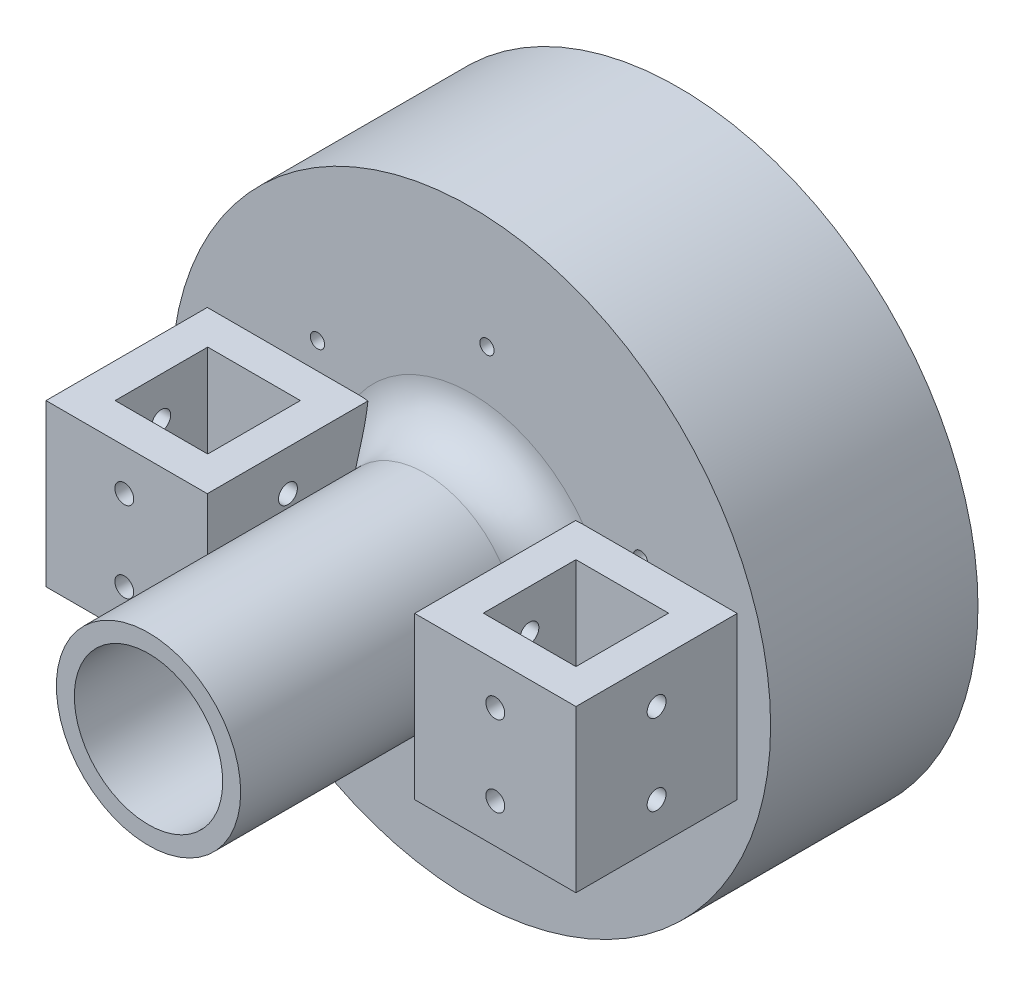
SolidWorks part; units mm, degrees
ref_plane "Front Plane" through (0, 0, 0) normal (0, 0, 1) x (1, 0, 0)
ref_plane "Top Plane" through (0, 0, 0) normal (0, 1, 0) x (1, 0, 0)
ref_plane "Right Plane" through (0, 0, 0) normal (1, 0, 0) x (0, 0, -1)
sketch "Sketch1" plane through (0, 0, 0) normal (0, 0, 1) x (1, 0, 0)
  line L0 (-60.923, -22.6581) -> (60.923, 22.6581) construction
  circle A0 centre (0, 0) radius 65
  circle A6 centre (-3.4488, -40.4788) radius 1.55
  circle A7 centre (0, 0) radius 16.5
  circle A11 centre (-36.7801, -17.2527) radius 1.55
  circle A12 centre (-33.3313, 23.2262) radius 1.55
  circle A13 centre (3.4488, 40.4788) radius 1.55
  circle A14 centre (36.7801, 17.2527) radius 1.55
  circle A15 centre (33.3313, -23.2262) radius 1.55
  point P18 (0, 0)
  point P20 (0, 0)
  point P36 (0, 0)
  dimension "D1" = 130
  dimension "D2" = 6
  dimension "D5" = 33
  dimension "D3" = 40.6255
extrude "Boss-Extrude1" add sketch "Sketch1" along normal blind 10
sketch "Sketch2" plane through (0, 0, 10) normal (0, 0, 1) x (1, 0, 0)
  circle A0 centre (0, 0) radius 20
  circle A1 centre (0, 0) radius 16.1
  dimension "D1" = 40
  dimension "D2" = 32.2
extrude "Boss-Extrude2" add sketch "Sketch2" along normal blind 70
sketch "Sketch3" plane through (0, 0, 0) normal (0, 0, -1) x (-1, 0, 0)
  circle A0 centre (0, 0) radius 45.25
  circle A1 centre (0, 0) radius 65
  dimension "D1" = 90.5
extrude "Boss-Extrude3" add sketch "Sketch3" along normal blind 35
sketch "Sketch4" plane through (0, 0, 10) normal (0, 0, 1) x (1, 0, 0)
  line L0 (-65, 0) -> (65, 0) construction
  line L1 (-57.2457, 17.5) -> (-22.2457, 17.5)
  line L2 (-57.2457, 17.5) -> (-57.2457, -17.5)
  line L3 (-57.2457, -17.5) -> (-22.2457, -17.5)
  line L4 (-22.2457, 17.5) -> (-22.2457, -17.5)
  line L5 (-57.2457, 17.5) -> (-22.2457, -17.5) construction
  line L6 (-57.2457, -17.5) -> (-22.2457, 17.5) construction
  line L7 (22.7543, 17.5) -> (57.7543, 17.5)
  line L8 (22.7543, 17.5) -> (22.7543, -17.5)
  line L9 (22.7543, -17.5) -> (57.7543, -17.5)
  line L10 (57.7543, 17.5) -> (57.7543, -17.5)
  line L11 (22.7543, 17.5) -> (57.7543, -17.5) construction
  line L12 (22.7543, -17.5) -> (57.7543, 17.5) construction
  circle A0 centre (40.3888, -6.3107) radius 1.55 construction
  circle A1 centre (-39.7457, -0.7631) radius 1.55 construction
  circle A2 centre (0, 0) radius 65 construction
  point P21 (40.2543, 0)
  point P22 (-39.7457, 0)
  point P23 (-22.2457, 0)
  dimension "D1" = 35
  dimension "D2" = 35
  dimension "D3" = 35
  dimension "D4" = 35
  dimension "D5" = 45
  dimension "D6" = 22.2457
extrude "Boss-Extrude4" add sketch "Sketch4" along normal blind 35
sketch "Sketch5" plane through (0, 17.5, 0) normal (0, 1, 0) x (1, 0, 0)
  line L0 (57.7543, -45) -> (57.7543, -10) construction
  line L1 (30.1543, -17.4) -> (50.2543, -17.4)
  line L2 (30.1543, -17.4) -> (30.1543, -37.5)
  line L3 (30.1543, -37.5) -> (50.2543, -37.5)
  line L4 (50.2543, -17.4) -> (50.2543, -37.5)
  line L5 (30.1543, -17.4) -> (50.2543, -37.5) construction
  line L6 (30.1543, -37.5) -> (50.2543, -17.4) construction
  line L7 (-49.7457, -17.4) -> (-29.6457, -17.4)
  line L8 (-49.7457, -17.4) -> (-49.7457, -37.5)
  line L9 (-49.7457, -37.5) -> (-29.6457, -37.5)
  line L10 (-29.6457, -17.4) -> (-29.6457, -37.5)
  line L11 (-49.7457, -17.4) -> (-29.6457, -37.5) construction
  line L12 (-49.7457, -37.5) -> (-29.6457, -17.4) construction
  line L13 (57.7543, -45) -> (22.7543, -45) construction
  line L14 (-57.2457, -45) -> (-57.2457, -10) construction
  line L15 (-22.2457, -45) -> (-57.2457, -45) construction
  point P0 (40.2043, -27.45)
  point P5 (-39.6957, -27.45)
  dimension "D1" = 20.1
  dimension "D2" = 20.1
  dimension "D3" = 7.5
  dimension "D4" = 7.5
  dimension "D5" = 20.1
  dimension "D6" = 20.1
  dimension "D7" = 7.5
  dimension "D8" = 7.5
extrude "Cut-Extrude1" cut sketch "Sketch5" against normal blind 40
fillet "Fillet1" radius 10 1 edges at (20, 0, 10)
sketch "Sketch6" plane through (57.7543, 0, 0) normal (1, 0, 0) x (0, 0, -1)
  line L0 (-27.5, 17.5) -> (-27.5, -17.5) construction
  line L1 (-45, 17.5) -> (-10, 17.5) construction
  line L2 (-45, -17.5) -> (-10, -17.5) construction
  line L3 (-45, 0) -> (-10, 0) construction
  line L4 (-45, -17.5) -> (-45, 17.5) construction
  line L5 (-10, 65) -> (-10, -65) construction
  circle A0 centre (-27.5, 8.75) radius 2.05
  circle A1 centre (-27.5, -8.75) radius 2.05
  point P16 (-27.5, 0)
  dimension "D1" = 4.1
  dimension "D2" = 4.1
  dimension "D3" = 8.75
  dimension "D4" = 8.75
extrude "Cut-Extrude2" cut sketch "Sketch6" against normal blind 127
sketch "Sketch7" plane through (0, 0, 45) normal (0, 0, 1) x (1, 0, 0)
  line L0 (24.367, -17.5) -> (57.7543, -17.5) construction
  line L1 (22.7543, 17.5) -> (22.7543, -17.5) construction
  line L2 (0, 0) -> (0, -6.0051) construction
  circle A0 centre (40.2543, 8.5) radius 2.05
  circle A1 centre (40.2543, -9) radius 2.05
  circle A2 centre (-40.2543, -9) radius 2.05
  circle A3 centre (-40.2543, 8.5) radius 2.05
  dimension "D1" = 4.1
  dimension "D2" = 4.1
  dimension "D3" = 17.5
  dimension "D4" = 8.5
  dimension "D5" = 17.5
extrude "Cut-Extrude3" cut sketch "Sketch7" along normal blind 1 and the other way blind 16
